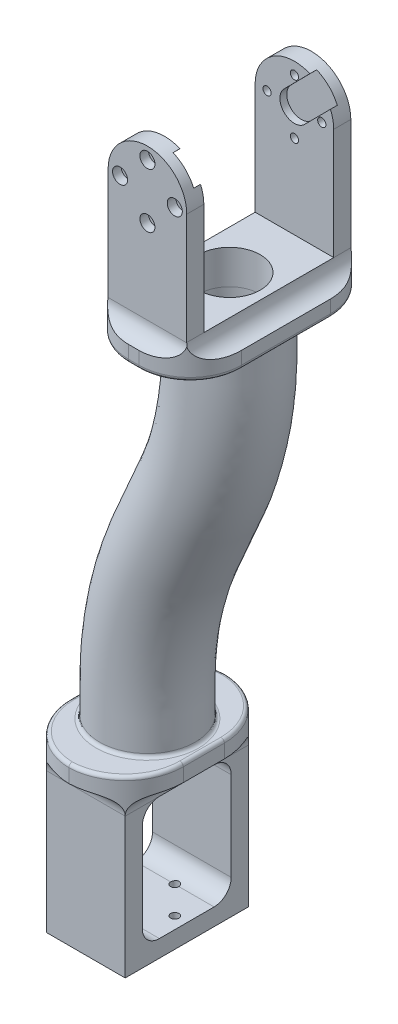
SolidWorks part; units mm, degrees
note: The reader was unsure of these and kept them because the rebuilt part matched: shared geometry of "Croquis88<4>", "Croquis112<2>".
material "PLA"
ref_plane "Alzado" through (0, 0, 0) normal (0, 0, 1) x (1, 0, 0)
ref_plane "Planta" through (0, 0, 0) normal (0, 1, 0) x (1, 0, 0)
ref_plane "Vista lateral" through (0, 0, 0) normal (1, 0, 0) x (0, 0, -1)
sketch "Croquis1" plane through (0, 0, 0) normal (0, 1, 0) x (1, 0, 0)
  line L1 (-11.5, 18) -> (11.5, 18)
  line L2 (-11.5, 18) -> (-11.5, -18)
  line L3 (-11.5, -18) -> (11.5, -18)
  line L4 (11.5, 18) -> (11.5, -18)
  line L5 (-11.5, 18) -> (11.5, -18) construction
  line L6 (-11.5, -18) -> (11.5, 18) construction
  point P0 (0, 0)
  dimension "D1" = 23
  dimension "D2" = 36
extrude "Saliente-Extruir1" add sketch "Croquis1" along normal blind 46
sketch "Croquis24" plane through (0, 0, 0) normal (0, -1, 0) x (1, 0, 0)
  line L0 (0, 19.0875) -> (0, -13.2025) construction
  line L1 (-10.9974, 0) -> (10.466, 0) construction
  circle A0 centre (0, 0) radius 8
  dimension "D1" = 16
hole_wizard "Taladro de margen para M23" positions "Croquis3D3" profile "Croquis26" hole size "M2" standard "ISO"
sketch3d "Croquis3D3"
  line L0 (0, 0, 19.0875) -> (0, 0, -13.2025) construction
  line L1 (-10.9974, 0, 0) -> (10.466, 0, 0) construction
  circle A0 centre (0, 0, 0) radius 8 construction
  point P0 (0, 0, 8)
  point P4 (0, -8, 0)
  point P7 (8, 0, 0)
  point P11 (0, 0, -8)
  point P13 (-8, 0, 0)
sketch "Croquis26" plane through (0, 0, 8) normal (1, 0, 0) x (0, 0, -1)
  line L0 (0, 0) -> (0, 10.721)
  line L1 (0, 10.721) -> (1.2, 10)
  line L2 (1.2, 10) -> (1.2, 0)
  line L5 (1.2, 0) -> (0, 0)
  line L10 (0, 10.721) -> (-1.2, 10) construction
  line L11 (0, -6.35) -> (0, 107.95) construction
  dimension "Diámetro de taladro" = 2.4
  dimension "Profundidad de taladro" = 10
  dimension "Ángulo de perforador" = 118
sketch "Croquis27" plane through (0, 0, 0) normal (0, -1, 0) x (1, 0, 0)
  circle A0 centre (0, 0) radius 4
  dimension "D1" = 8
extrude "Cortar-Extruir3" cut sketch "Croquis27" against normal blind 2
sketch "Croquis29" plane through (-11.5, 0, 0) normal (-1, 0, 0) x (0, 0, 1)
  line L4 (13, 41) -> (-13, 41)
  line L8 (-13, 5) -> (13, 5)
  line L9 (13, 5) -> (13, 41)
  line L11 (-13, 41) -> (-13, 5)
  line L12 (-13, 5) -> (13, 5)
  line L13 (13, 5) -> (13, 41)
  line L15 (-13, 41) -> (-13, 5)
  line L18 (13, 41) -> (-13, 41)
  dimension "D1" = 5
extrude "Cortar-Extruir5" cut sketch "Croquis29" against normal through all
sketch "Croquis35" plane through (0, 5, 0) normal (0, 1, 0) x (1, 0, 0)
  line L12 (-9.5, 11) -> (-9.5, -11)
  line L13 (-9.5, -11) -> (9.5, -11)
  line L14 (9.5, -11) -> (9.5, 11)
  line L15 (9.5, 11) -> (-9.5, 11)
  line L16 (-9.5, 11) -> (-9.5, -11)
  line L17 (-9.5, -11) -> (9.5, -11)
  line L18 (9.5, -11) -> (9.5, 11)
  line L19 (9.5, 11) -> (-9.5, 11)
  dimension "D1" = 2
sketch "Croquis75" plane through (0, 46, 0) normal (0, 1, 0) x (1, 0, 0)
  line L1 (-16.5, 23) -> (16.5, 23)
  line L2 (-16.5, 23) -> (-16.5, -23)
  line L3 (-16.5, -23) -> (16.5, -23)
  line L4 (16.5, 23) -> (16.5, -23)
  line L5 (-16.5, 23) -> (16.5, -23) construction
  line L6 (-16.5, -23) -> (16.5, 23) construction
  point P0 (0, 0)
  dimension "D1" = 33
  dimension "D2" = 46
extrude "Saliente-Extruir11" add sketch "Croquis75" along normal blind 5
sketch "Croquis85" plane through (0, 51, 0) normal (0, 1, 0) x (1, 0, 0)
  circle A0 centre (0, 0) radius 14
  dimension "D1" = 28
sketch "Croquis88" plane through (0, 0, 0) normal (0, 0, 1) x (1, 0, 0)
  line L0 (0, 51) -> (0, 60.1319)
  line L1 (14, 51) -> (-14, 51) construction
  line L2 (8.3461, 100.1264) -> (15.6539, 116.8736)
  line L3 (24, 156.8681) -> (24, 166)
  arc A0 (15.6539, 116.8736) -> (24, 156.8681) centre (-76, 156.8681) ccw
  arc A1 (0, 60.1319) -> (8.3461, 100.1264) centre (100, 60.1319) cw
  point P9 (24, 136)
  point P12 (0, 81)
  dimension "D5" = 100
  dimension "D1" = 24
  dimension "D2" = 30
  dimension "D3" = 30
  dimension "D4" = 115
sweep "Barrer3" add profiles "Croquis85" path "Croquis88"
sketch "Croquis90" plane through (0, 166, 0) normal (0, 1, 0) x (1, 0, 0)
  line L1 (7.5, -28) -> (40.5, -28)
  line L2 (7.5, -28) -> (7.5, 28)
  line L3 (7.5, 28) -> (40.5, 28)
  line L4 (40.5, -28) -> (40.5, 28)
  line L5 (7.5, -28) -> (40.5, 28) construction
  line L6 (7.5, 28) -> (40.5, -28) construction
  circle A0 centre (24, 0) radius 14 construction
  circle A1 centre (24, 0) radius 14
  dimension "D1" = 56
  dimension "D2" = 33
extrude "Saliente-Extruir12" add sketch "Croquis90" along normal blind 5 separate body
sketch "Croquis96" plane through (0, 171, 0) normal (0, 1, 0) x (1, 0, 0)
  circle A0 centre (24, 0) radius 14
  dimension "D1" = 28
extrude "Saliente-Extruir16" add sketch "Croquis96" against normal blind 5
sketch "Croquis98" plane through (0, 171, 0) normal (0, 1, 0) x (1, 0, 0)
  line L0 (3, 0) -> (45, 0) construction
  line L1 (24, 28) -> (24, -28) construction
  line L3 (12.5, 24) -> (35.5, 24)
  line L4 (40.5, -28) -> (40.5, 28)
  line L5 (40.5, 28) -> (7.5, 28)
  line L6 (7.5, 28) -> (7.5, -28)
  line L7 (7.5, -28) -> (40.5, -28)
  line L8 (40.5, -28) -> (40.5, 28)
  line L9 (40.5, 28) -> (7.5, 28)
  line L10 (7.5, 28) -> (7.5, -28)
  line L11 (7.5, -28) -> (40.5, -28)
  line L12 (12.5, 24) -> (12.5, -24)
  line L13 (12.5, -24) -> (35.5, -24)
  line L14 (35.5, 24) -> (35.5, -24)
  line L15 (12.5, 24) -> (35.5, -24) construction
  line L16 (12.5, -24) -> (35.5, 24) construction
  point P9 (24, 0)
  dimension "D2" = 48
  dimension "D3" = 23
  dimension "D1" = 0
extrude "Saliente-Extruir17" add sketch "Croquis98" along normal blind 5 contours L12 L13 L14 L3
sketch "Croquis100" plane through (0, 176, 0) normal (0, 1, 0) x (1, 0, 0)
  line L0 (35.5, 24) -> (35.5, -24) construction
  line L1 (12.5, 24) -> (35.5, 24)
  line L2 (12.5, 24) -> (12.5, 19)
  line L3 (12.5, 19) -> (35.5, 19)
  line L4 (35.5, 24) -> (35.5, 19)
  dimension "D1" = 5
extrude "Saliente-Extruir18" add sketch "Croquis100" along normal blind 32.5
sketch "Croquis106" plane through (0, 0, -24) normal (0, 0, -1) x (-1, 0, 0)
  line L0 (-35.5, 208.5) -> (-12.5, 208.5) construction
  line L1 (-35.5, 208.5) -> (-12.5, 208.5)
  arc A0 (-12.5, 208.5) -> (-35.5, 208.5) centre (-24, 208.5) ccw
  dimension "D1" = 23
extrude "Saliente-Extruir19" add sketch "Croquis106" against normal blind 5
fillet "Redondeo1" radius 17 4 edges at (16.5, 48.5, -23) (16.5, 48.5, 23) (-16.5, 48.5, 23) (-16.5, 48.5, -23)
fillet "Redondeo2" radius 5 2 edges at (11.5, 46, 0) (-11.5, 46, 0)
fillet "Redondeo4" radius 5 4 edges at (0, 5, 13) (0, 5, -13) (0, 41, 13) (0, 41, -13)
fillet "Redondeo5" radius 1 7 edges at (0, 51, 14) (-16.5, 51, 0) (-11.6963, 51, -17.8427) (11.6963, 51, -17.8427) (16.5, 51, 0) (11.6963, 51, 17.8427) (-11.6963, 51, 17.8427)
sketch "Croquis109" plane through (0, 0, -24) normal (0, 0, -1) x (-1, 0, 0)
  line L0 (-24, 218.5675) -> (-24, 197.953) construction
  line L1 (-33.7306, 208.5) -> (-13.9805, 208.5) construction
  circle A0 centre (-24, 208.5) radius 8
  dimension "D1" = 16
hole_wizard "Refrentado para tornillo con cabeza plana de M21" positions "Croquis3D4" profile "Croquis110" counterbore size "M2" standard "ISO" end condition through all
sketch3d "Croquis3D4"
  line L0 (24, 218.5675, -24) -> (24, 197.953, -24) construction
  line L1 (33.7306, 208.5, -24) -> (13.9805, 208.5, -24) construction
  circle A0 centre (24, 208.5, -24) radius 8 construction
  point P0 (24, 216.5, -24)
  point P4 (24, 208.5, -32)
  point P7 (16, 208.5, -24)
  point P11 (24, 200.5, -24)
  point P13 (32, 208.5, -24)
sketch "Croquis110" plane through (24, 216.5, -24) normal (1, 0, 0) x (0, 1, 0)
  line L0 (0, 0) -> (0, 52)
  line L1 (0, 52) -> (1.2, 52)
  line L3 (1.2, 52) -> (1.2, 2.5)
  line L4 (1.2, 2.5) -> (2.2, 2.5)
  line L5 (2.2, 2.5) -> (2.2, 0)
  line L7 (2.2, 0) -> (0, 0)
  line L11 (0, -6.35) -> (0, 107.95) construction
  dimension "Diámetro de taladro hasta el siguiente" = 2.4
  dimension "Profundidad de taladro hasta el siguiente" = 52
  dimension "Diámetro de refrentado" = 4.4
  dimension "Profundidad de refrentado" = 2.5
sketch "Croquis111" plane through (0, 0, -19) normal (0, 0, 1) x (1, 0, 0)
  line L0 (28.4972, 219.0842) -> (21.1405, 211.6441)
  line L1 (34.5385, 213.1032) -> (26.7843, 205.2891)
  arc A0 (21.1405, 211.6441) -> (26.7843, 205.2891) centre (24, 208.5) ccw
  arc A1 (28.4972, 219.0842) -> (34.5385, 213.1032) centre (24, 208.5) cw
  arc A2 (35.5, 208.5) -> (12.5, 208.5) centre (24, 208.5) ccw construction
  dimension "D1" = 8.5
extrude "Cortar-Extruir7" cut sketch "Croquis111" against normal blind 2
mirror "Simetría1" about plane through (0, 0, 0) normal (0, 0, 1) of "Saliente-Extruir17", "Saliente-Extruir18", "Saliente-Extruir19", "Refrentado para tornillo con cabeza plana de M21", "Cortar-Extruir7"
fillet "Redondeo8" radius 5 2 edges at (35.5, 171, 0) (12.5, 171, 0)
fillet "Redondeo9" radius 5 2 edges at (24, 171, -24) (24, 171, 24)
sketch "Croquis112" plane through (0, 166, 0) normal (0, -1, 0) x (1, 0, 0)
  circle A0 centre (24, 0) radius 9
  dimension "D1" = 18
sweep "Cortar-Barrer1" cut profiles "Croquis112" path "Croquis88<4>"
sketch "Croquis88<4>" plane through (0, 0, 0) normal (0, 0, 1) x (1, 0, 0) same geometry as "Croquis88"
extrude "Cortar-Extruir8" cut sketch "Croquis112<2>" against normal blind 11
sketch "Croquis112<2>" plane through (0, 166, 0) normal (0, -1, 0) x (1, 0, 0) same geometry as "Croquis112"
sketch "Croquis113" plane through (0, 41, 0) normal (0, -1, 0) x (1, 0, 0)
  circle A1 centre (0, 0) radius 9
  dimension "D1" = 18
extrude "Cortar-Extruir9" cut sketch "Croquis113" against normal blind 11
fillet "Redondeo12" radius 5 2 edges at (0, 46, 18) (0, 46, -18)
fillet "Redondeo13" radius 15 4 edges at (7.5, 168.5, 28) (7.5, 168.5, -28) (40.5, 168.5, -28) (40.5, 168.5, 28)
fillet "Redondeo14" radius 1.25 9 edges at (24, 166, 14) (36.1066, 166, 23.6066) (40.5, 166, 0) (36.1066, 166, -23.6066) (24, 166, -28) (11.8934, 166, -23.6066) (7.5, 166, 0) (11.8934, 166, 23.6066) (24, 166, 28)
equation "\"42.5.00mm\"=45"
